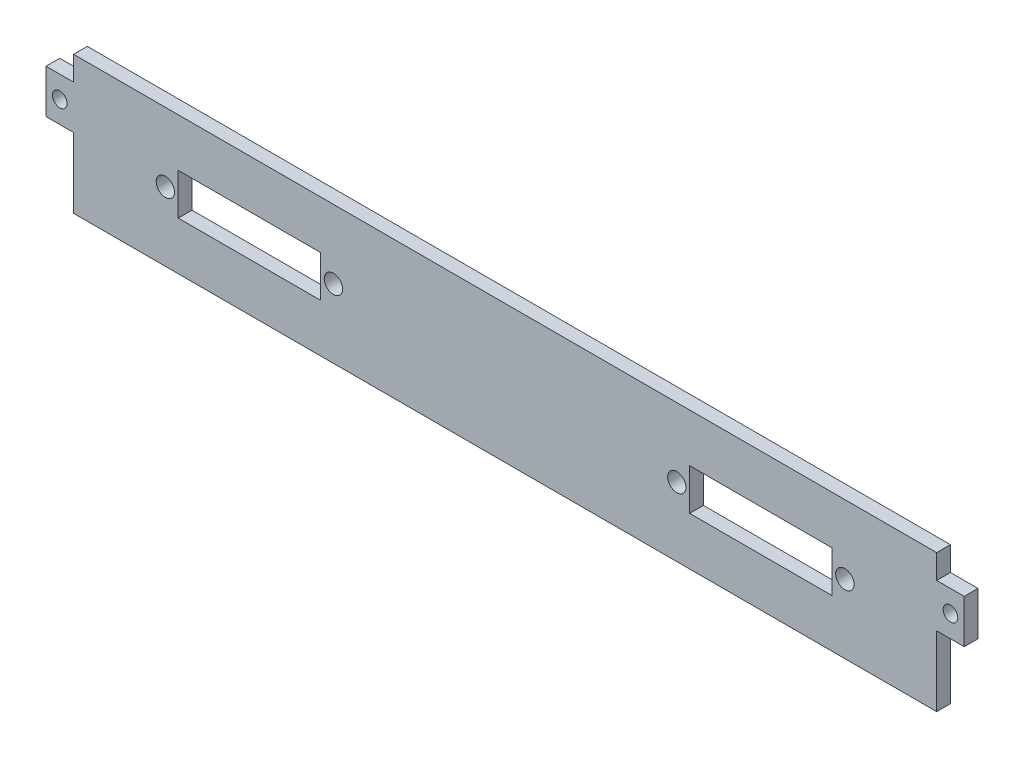
SolidWorks part; units mm, degrees
material "Balsa"
ref_plane "Plano frontal" through (0, 0, 0) normal (0, 0, 1) x (1, 0, 0)
ref_plane "Plano superior" through (0, 0, 0) normal (0, 1, 0) x (1, 0, 0)
ref_plane "Plano direito" through (0, 0, 0) normal (1, 0, 0) x (0, 0, -1)
sketch "Esboço1" plane through (0, 0, 0) normal (0, 0, 1) x (1, 0, 0)
  line L0 (-94, 0.25) -> (-94, -15)
  line L1 (-94, 15) -> (94, 15)
  line L2 (-94, 15) -> (-94, 9.75)
  line L3 (-94, -15) -> (94, -15)
  line L4 (94, 15) -> (94, 9.75)
  line L5 (-94, 15) -> (94, -15) construction
  line L6 (-94, -15) -> (94, 15) construction
  line L7 (-94, 9.75) -> (-100, 9.75)
  line L8 (0, 15) -> (0, -15) construction
  line L9 (-94, 0.25) -> (-100, 0.25)
  line L10 (-100, 9.75) -> (-100, 0.25)
  line L11 (94, 9.75) -> (100, 9.75)
  line L12 (94, 0.25) -> (100, 0.25)
  line L13 (100, 9.75) -> (100, 0.25)
  line L14 (94, 0.25) -> (94, -15)
  line L15 (-100, 9.75) -> (-94, 0.25) construction
  line L16 (-74, 0) -> (-37.4, 0) construction
  line L17 (71.2, -4.5) -> (40.2, 4.5) construction
  line L18 (-71.2, 4.5) -> (-40.2, 4.5)
  line L19 (-71.2, 4.5) -> (-71.2, -4.5)
  line L20 (-71.2, -4.5) -> (-40.2, -4.5)
  line L21 (-40.2, 4.5) -> (-40.2, -4.5)
  line L22 (-71.2, 4.5) -> (-40.2, -4.5) construction
  line L23 (-71.2, -4.5) -> (-40.2, 4.5) construction
  line L24 (71.2, 4.5) -> (40.2, -4.5) construction
  line L25 (74, 0) -> (37.4, 0) construction
  line L26 (40.2, 4.5) -> (40.2, -4.5)
  line L27 (71.2, -4.5) -> (40.2, -4.5)
  line L28 (71.2, 4.5) -> (71.2, -4.5)
  line L29 (71.2, 4.5) -> (40.2, 4.5)
  circle A0 centre (-97, 5) radius 1.6
  circle A1 centre (97, 5) radius 1.6
  circle A2 centre (-74, 0) radius 2
  circle A3 centre (-37.4, 0) radius 2
  circle A4 centre (37.4, 0) radius 2
  circle A5 centre (74, 0) radius 2
  point P0 (0, 0)
  point P24 (-55.7, 0)
  point P33 (0, 0)
  point P38 (55.7, 0)
  dimension "D6" = 3.2
  dimension "D7" = 4
  dimension "D1" = 188
  dimension "D2" = 30
  dimension "D3" = 9.5
  dimension "D4" = 6
  dimension "D5" = 5.25
  dimension "D8" = 36.6
  dimension "D9" = 15
  dimension "D10" = 20
  dimension "D11" = 9
  dimension "D12" = 31
extrude "Ressalto-extrusão1" add sketch "Esboço1" along normal blind 3
